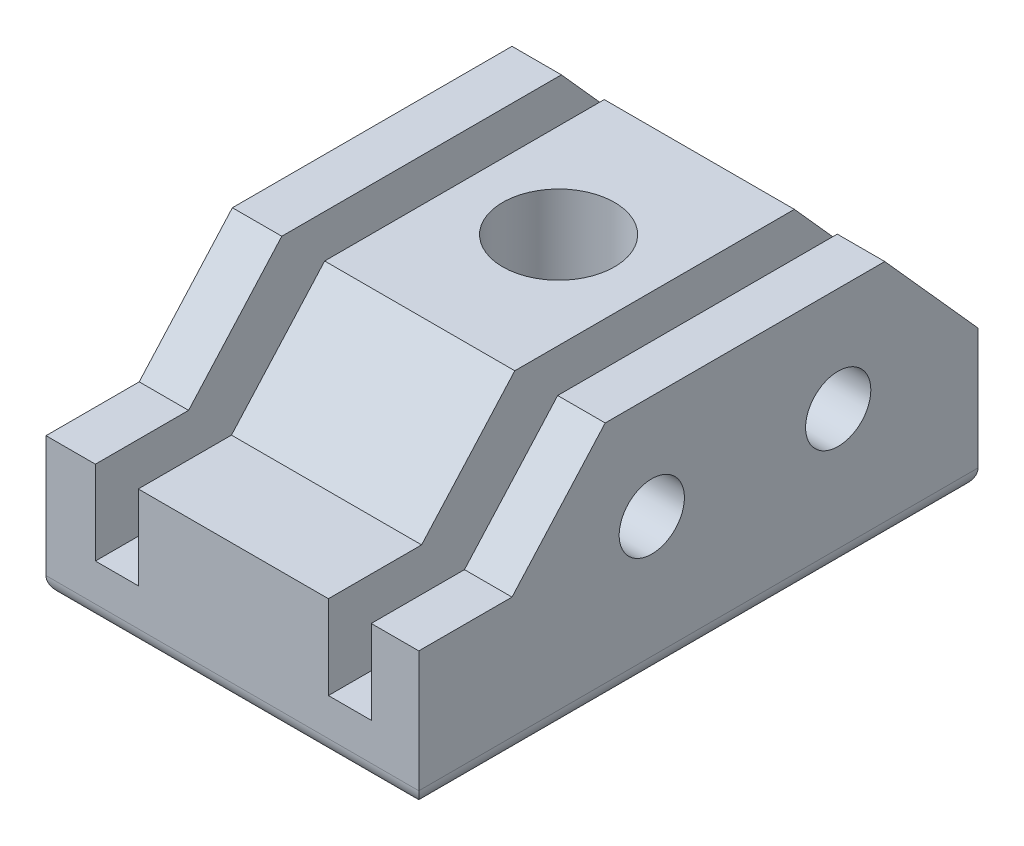
SolidWorks part; units mm, degrees
ref_plane "Front Plane" through (0, 0, 0) normal (0, 0, 1) x (1, 0, 0)
ref_plane "Top Plane" through (0, 0, 0) normal (0, 1, 0) x (1, 0, 0)
ref_plane "Right Plane" through (0, 0, 0) normal (1, 0, 0) x (0, 0, -1)
sketch "Sketch1" plane through (0, 0, 0) normal (1, 0, 0) x (0, 0, -1)
  line L1 (0, 0) -> (63.5, 0)
  line L2 (0, 0) -> (0, 6.35)
  line L3 (0, 6.35) -> (63.5, 6.35)
  line L4 (63.5, 0) -> (63.5, 6.35)
  dimension "D1" = 6.35
  dimension "D2" = 63.5
extrude "Boss-Extrude1" add sketch "Sketch1" against normal blind 50.8
sketch "Sketch2" plane through (0, 0, 0) normal (1, 0, 0) x (0, 0, -1)
  line L0 (0, 6.35) -> (0, 19.05)
  line L1 (0, 19.05) -> (12.7, 33.249)
  line L2 (12.7, 33.249) -> (50.8, 33.249)
  line L3 (50.8, 33.249) -> (63.5, 19.05)
  line L4 (63.5, 19.05) -> (63.5, 6.35)
  line L5 (63.5, 6.35) -> (0, 6.35)
  point P7 (31.75, 33.249)
  point P10 (31.75, 6.35)
  dimension "D1" = 38.1
  dimension "D2" = 12.7
  dimension "D3" = 12.7
  dimension "D4" = 19.05
  dimension "D5" = 19.05
extrude "Boss-Extrude2" add sketch "Sketch2" against normal blind 50.8
sketch "Sketch10" plane through (0, 0, -63.5) normal (0, 0, -1) x (-1, 0, 0)
  line L0 (25.4, 0) -> (25.4, 33.249) construction
  line L1 (50.8, 33.249) -> (0, 33.249) construction
  line L3 (6.477, 7.62) -> (6.477, 33.249)
  line L4 (6.477, 33.249) -> (12.319, 33.249)
  line L5 (12.319, 7.62) -> (12.319, 33.249)
  line L6 (6.477, 7.62) -> (12.319, 7.62)
  line L8 (50.8, 0) -> (0, 0) construction
  point P11 (12.319, 7.62)
  dimension "D1" = 7.62
  dimension "D2" = 5.842
  dimension "D3" = 13.081
extrude "Cut-Extrude1" cut sketch "Sketch10" against normal through all
pattern_linear "LPattern3" count 2 spacing 31.75 along (-1, 0, 0) of "Cut-Extrude1"
sketch "Sketch11" plane through (0, 0, 0) normal (1, 0, 0) x (0, 0, -1)
  circle A0 centre (19.05, 19.05) radius 4.445
  circle A1 centre (19.05, 19.05) radius 7.9375 construction
  circle A2 centre (44.45, 19.05) radius 4.445
  circle A3 centre (44.45, 19.05) radius 7.9375 construction
  dimension "D1" = 8.89
  dimension "D3" = 15.875
  dimension "D6" = 15.875
  dimension "D2" = 6.35
  dimension "D5" = 6.35
extrude "Cut-Extrude2" cut sketch "Sketch11" against normal through all
sketch "Sketch14" plane through (0, 33.249, 0) normal (0, 1, 0) x (1, 0, 0)
  line L3 (-38.227, 12.7) -> (-38.227, 50.8) construction
  point P0 (-25.781, 31.75)
  point P4 (-38.227, 31.75)
  dimension "D1" = 12.446
sketch "Sketch17" plane through (0, 40.0201, -44.7438) normal (0, 0.6667, -0.7454) x (-1, 0, 0)
  line L0 (12.319, -28.1343) -> (12.319, -9.0843) construction
  line L1 (38.227, -9.0843) -> (12.319, -9.0843) construction
  point P0 (25.273, -18.6093)
  point P4 (12.319, -18.6093)
  point P7 (25.273, -9.0843)
sketch "Sketch18" plane through (0, 8.4667, 9.466) normal (0, 0.6667, 0.7454) x (1, 0, 0)
  line L0 (-12.319, 33.249) -> (-12.319, 14.199) construction
  line L1 (-38.227, 33.249) -> (-12.319, 33.249) construction
  point P0 (-25.273, 23.724)
  point P1 (-25.273, 23.724)
  point P4 (-12.319, 23.724)
  point P7 (-25.273, 33.249)
ref_plane "Plane2" through (0, 33.02, 0) normal (0, -1, 0) x (-1, 0, 0)
sketch "Sketch22" plane through (0, 0, 0) normal (0, 0, 1) x (1, 0, 0)
  line L0 (-50.8, 19.05) -> (-50.8, 0) construction
  line L1 (0, 0) -> (-50.8, 0)
  line L2 (0, 0) -> (0, 7.62)
  line L3 (-6.477, 7.62) -> (-12.319, 7.62)
  line L4 (-50.8, 0) -> (-50.8, 7.62)
  line L5 (-38.227, 7.62) -> (-38.227, 19.05)
  line L6 (-38.227, 19.05) -> (-12.319, 19.05)
  line L7 (-12.319, 19.05) -> (-12.319, 7.62)
  line L8 (-38.227, 7.62) -> (-44.069, 7.62)
  line L9 (-50.8, 7.62) -> (-50.8, 19.05)
  line L10 (-50.8, 19.05) -> (-44.069, 19.05)
  line L11 (-44.069, 19.05) -> (-44.069, 7.62)
  line L12 (-6.477, 7.62) -> (-6.477, 19.05)
  line L13 (-6.477, 19.05) -> (0, 19.05)
  line L14 (0, 19.05) -> (0, 7.62)
extrude "Boss-Extrude3" add sketch "Sketch22" along normal blind 12.7
sketch "Sketch23" plane through (0, 33.249, 0) normal (0, 1, 0) x (1, 0, 0)
  line L0 (-25.4, 63.5) -> (-25.4, -12.7) construction
  line L1 (-50.8, 63.5) -> (0, 63.5) construction
  line L2 (-50.8, -12.7) -> (0, -12.7) construction
  circle A0 centre (-25.4, 31.75) radius 7.62
  point P15 (-34.579, 50.8)
  dimension "D1" = 15.24
extrude "Cut-Extrude6" cut sketch "Sketch23" against normal through all
fillet "Fillet2" radius 2.54 4 edges at (-25.4, 0, -63.5) (-50.8, 0, -25.4) (-25.4, 0, 12.7) (0, 0, -25.4)
sketch "Sketch24" plane through (0, 0, 0) normal (0, -1, 0) x (1, 0, 0)
  line L0 (-20.4, -46.15) -> (-30.4, -46.15) construction
  line L1 (-25.4, -60.96) -> (-25.4, 10.16) construction
  line L2 (-48.26, -60.96) -> (-2.54, -60.96) construction
  line L3 (-2.54, 10.16) -> (-48.26, 10.16) construction
  line L4 (-20.4, 3.35) -> (-30.4, 3.35) construction
  circle A1 centre (-30.4, -46.15) radius 3.175
  circle A2 centre (-20.4, -46.15) radius 3.175
  circle A3 centre (-20.4, 3.35) radius 3.175
  circle A4 centre (-30.4, 3.35) radius 3.175
  circle A5 centre (-25.4, -31.75) radius 7.62 construction
  point P3 (-25.4, -46.15)
  point P12 (-25.4, 3.35)
  dimension "D2" = 6.35
  dimension "D1" = 10
  dimension "D3" = 49.5
  dimension "D4" = 14.4
extrude "Cut-Extrude7" cut sketch "Sketch24" against normal blind 10
